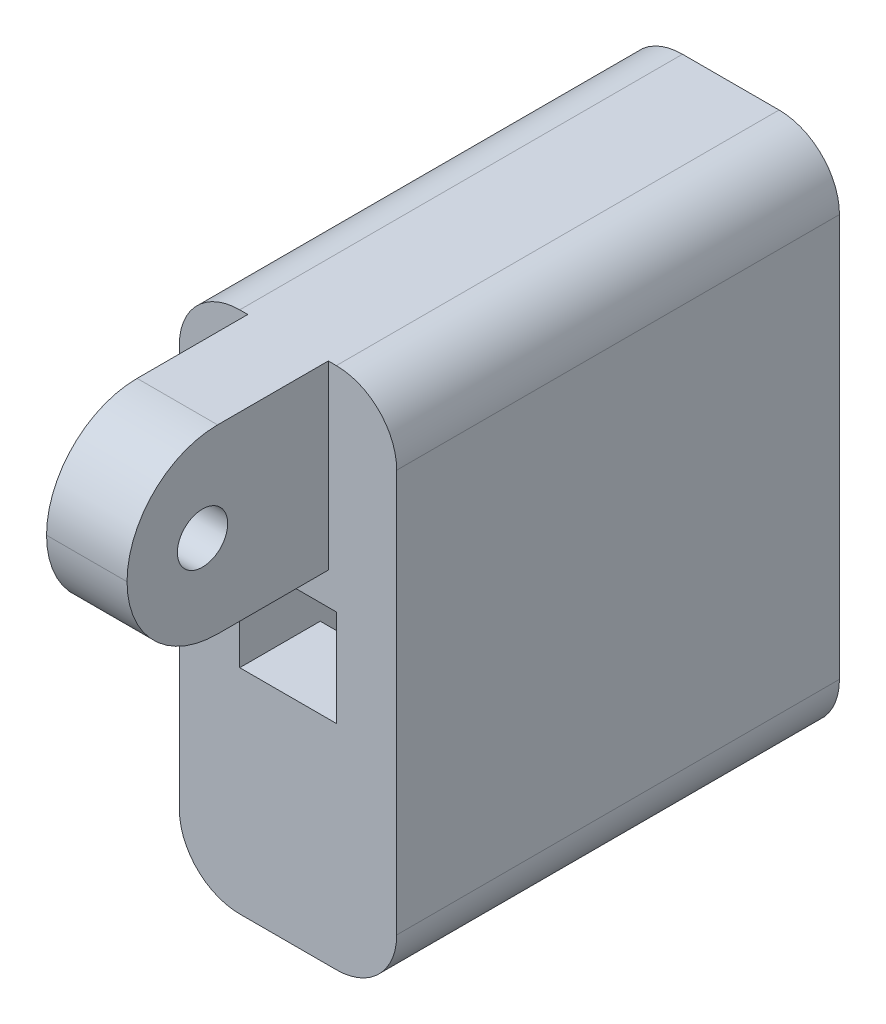
SolidWorks part; units mm, degrees
ref_plane "Front Plane" through (0, 0, 0) normal (0, 0, 1) x (1, 0, 0)
ref_plane "Top Plane" through (0, 0, 0) normal (0, 1, 0) x (1, 0, 0)
ref_plane "Right Plane" through (0, 0, 0) normal (1, 0, 0) x (0, 0, -1)
sketch "Sketch1" plane through (0, 0, 0) normal (0, 0, 1) x (1, 0, 0)
  line L1 (-2.4, -10) -> (2.4, -10)
  line L2 (-2.4, -10) -> (-2.4, 10)
  line L3 (-2.4, 10) -> (2.4, 10)
  line L4 (2.4, -10) -> (2.4, 10)
  line L5 (-2.4, -10) -> (2.4, 10) construction
  line L6 (-2.4, 10) -> (2.4, -10) construction
  line L7 (-5.4, -13) -> (5.4, -13)
  line L8 (-5.4, -13) -> (-5.4, 13)
  line L9 (-5.4, 13) -> (5.4, 13)
  line L10 (5.4, -13) -> (5.4, 13)
  line L11 (-5.4, -13) -> (5.4, 13) construction
  line L12 (-5.4, 13) -> (5.4, -13) construction
  line L13 (-2.4, 2.4) -> (2.4, 2.4)
  line L14 (-2.4, 2.4) -> (-2.4, -2.4)
  line L15 (-2.4, -2.4) -> (2.4, -2.4)
  line L16 (2.4, 2.4) -> (2.4, -2.4)
  line L17 (-2.4, 2.4) -> (2.4, -2.4) construction
  line L18 (-2.4, -2.4) -> (2.4, 2.4) construction
  point P0 (0, 0)
  point P6 (0, 0)
  point P11 (0, 0)
  dimension "D1" = 4.8
  dimension "D2" = 20
  dimension "D3" = 26
  dimension "D4" = 10.8
  dimension "D5" = 4.8
extrude "Boss-Extrude1" add sketch "Sketch1" along normal blind 18 contours L7 L10 L9 L8 L4 L1 L2 L3 region at (-5.1185, 0, 0)
sketch "Sketch2" plane through (0, 0, 18) normal (0, 0, 1) x (1, 0, 0)
  line L0 (2.4, -10) -> (2.4, 10) construction
  line L1 (-2.4, 2.4) -> (2.4, 2.4)
  line L2 (-2.4, 2.4) -> (-2.4, -2.4)
  line L3 (-2.4, -2.4) -> (2.4, -2.4)
  line L4 (2.4, 2.4) -> (2.4, -2.4)
  line L5 (-2.4, 2.4) -> (2.4, -2.4) construction
  line L6 (-2.4, -2.4) -> (2.4, 2.4) construction
  line L8 (-5.4, -13) -> (5.4, -13)
  line L9 (-5.4, -13) -> (-5.4, 13)
  line L10 (-5.4, 13) -> (5.4, 13)
  line L11 (5.4, -13) -> (5.4, 13)
  line L12 (-5.4, -13) -> (5.4, 13) construction
  line L13 (-5.4, 13) -> (5.4, -13) construction
  point P1 (0, 0)
  point P8 (0, 0)
  dimension "D1" = 4.8
extrude "Boss-Extrude2" add sketch "Sketch2" along normal blind 4
fillet "Fillet1" radius 3 4 edges at (-5.4, 13, 11) (5.4, 13, 11) (5.4, -13, 11) (-5.4, -13, 11)
sketch "Sketch5" plane through (0, 0, 22) normal (0, 0, 1) x (1, 0, 0)
  line L1 (2.4, 13) -> (-2.4, 13) construction
  line L2 (-2, 4) -> (2, 4)
  line L3 (-2, 4) -> (-2, 13)
  line L4 (-2, 13) -> (2, 13)
  line L5 (2, 4) -> (2, 13)
  line L6 (-2, 4) -> (2, 13) construction
  line L8 (-2, 13) -> (2, 4) construction
  line L9 (-5.4, 10) -> (-5.4, -10) construction
  point P0 (0, 8.5)
  dimension "D1" = 9
  dimension "D2" = 4
  dimension "D3" = 5.4
extrude "Boss-Extrude3" add sketch "Sketch5" along normal blind 10
fillet "Fillet2" radius 4.5 2 edges at (0, 13, 32) (0, 4, 32)
hole_wizard "Tap Drill for M3x0.5 Tap1" positions "3DSketch1" profile "Sketch7" hole size "M3x0.5" standard "ANSI Metric"
sketch3d "3DSketch1"
  line L0 (-2, 13, 27.5) -> (-2, 13, 22) construction
  point P0 (-2, 8.5027, 28.25)
  dimension "D1" = 3.75
  dimension "D2" = 4.4973
sketch "Sketch7" plane through (-2, 8.5027, 28.25) normal (0, 1, 0) x (0, 0, 1)
  line L0 (0, 0) -> (0, 4.7511)
  line L1 (0, 4.7511) -> (1.25, 4)
  line L2 (1.25, 4) -> (1.25, 0)
  line L5 (1.25, 0) -> (0, 0)
  line L10 (0, 4.7511) -> (-1.25, 4) construction
  line L11 (0, -6.35) -> (0, 107.95) construction
  dimension "Hole Dia." = 2.5
  dimension "Hole Depth" = 4
  dimension "Drill Angle" = 118
